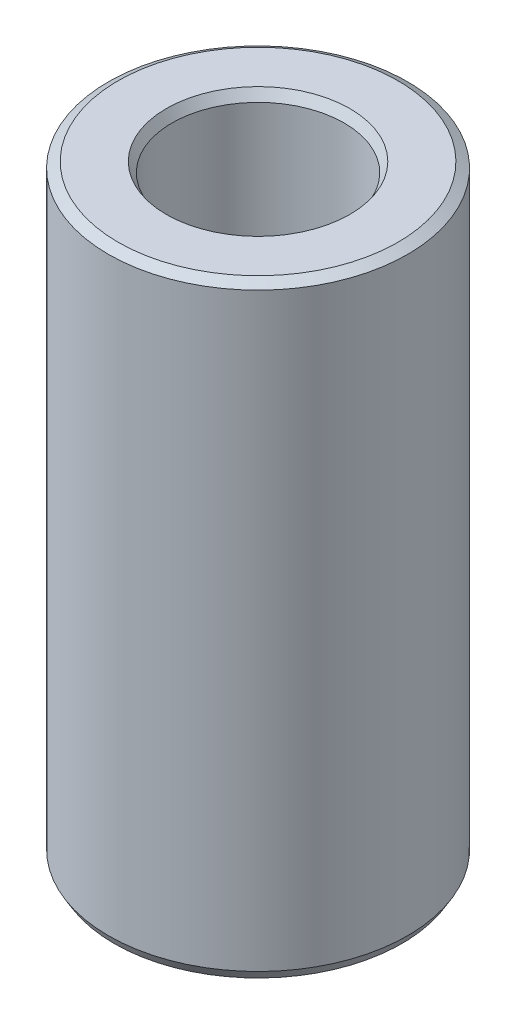
SolidWorks part; units mm, degrees
ref_plane "Front Plane" through (0, 0, 0) normal (0, 0, 1) x (1, 0, 0)
ref_plane "Top Plane" through (0, 0, 0) normal (0, 1, 0) x (1, 0, 0)
ref_plane "Right Plane" through (0, 0, 0) normal (1, 0, 0) x (0, 0, -1)
sketch "Sketch1" plane through (0, 0, 0) normal (0, 1, 0) x (1, 0, 0)
  circle A0 centre (0, 0) radius 20
  dimension "SLEEVE_OD" = 40
extrude "Boss-Extrude1" add sketch "Sketch1" along normal blind 80.953
sketch "Sketch2" plane through (0, 0, 0) normal (0, 1, 0) x (1, 0, 0)
  circle A0 centre (0, 0) radius 11.5118
  dimension "BORE_D" = 23.0236
extrude "Cut-Extrude1" cut sketch "Sketch2" along normal through all
chamfer "Chamfer1" distance 0.7592 angle 59.526 4 edges at (0, 80.953, 11.5118) (0, 0, 11.5118) (0, 0, 20) (0, 80.953, 20) first distance on face at (0, 80.953, 11.5118) first distance on face at (0, 0, 11.5118) first distance on face at (0, 80.953, 20)
